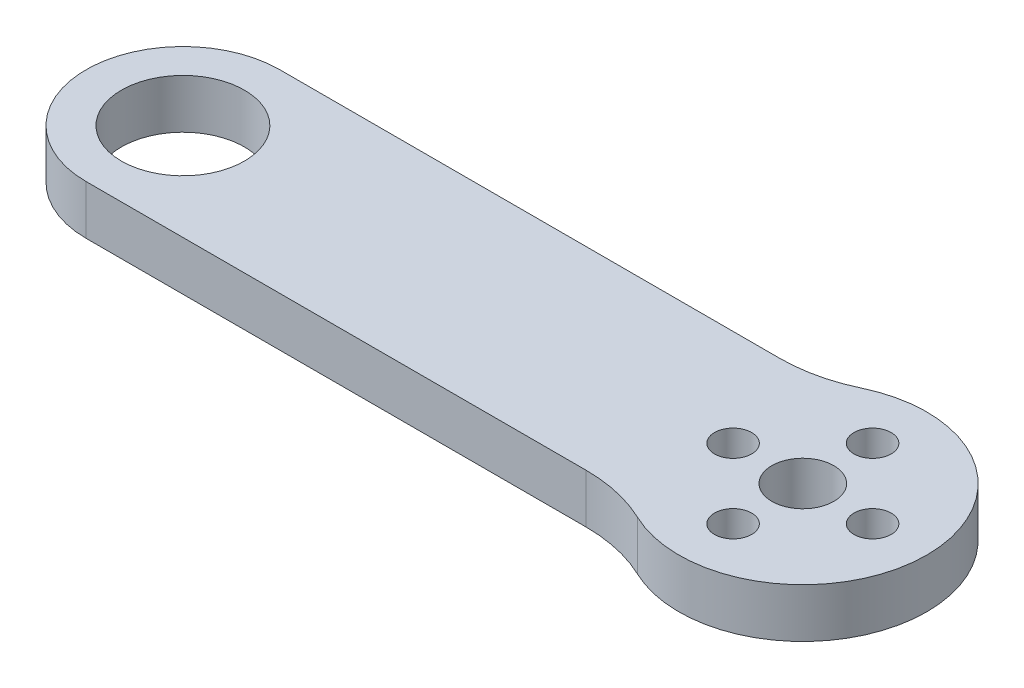
SolidWorks part; units mm, degrees
ref_plane "Front Plane" through (0, 0, 0) normal (0, 0, 1) x (1, 0, 0)
ref_plane "Top Plane" through (0, 0, 0) normal (0, 1, 0) x (1, 0, 0)
ref_plane "Right Plane" through (0, 0, 0) normal (1, 0, 0) x (0, 0, -1)
sketch "Sketch1" plane through (0, 0, 0) normal (0, 1, 0) x (1, 0, 0)
  line L0 (-7.7419, 6.25) -> (-40, 6.25)
  line L1 (0, 0) -> (-40, 0) construction
  line L2 (-40, -6.25) -> (-40, 6.25) construction
  line L3 (-40, -6.25) -> (-7.7419, -6.25)
  arc A0 (-3.4409, -7.2222) -> (-3.4409, 7.2222) centre (0, 0) ccw
  arc A1 (-40, -6.25) -> (-40, 6.25) centre (-40, 0) cw
  arc A2 (-7.7419, -6.25) -> (-3.4409, -7.2222) centre (-7.7419, -16.25) cw
  arc A3 (-7.7419, 6.25) -> (-3.4409, 7.2222) centre (-7.7419, 16.25) ccw
  circle A4 centre (-40, 0) radius 3.9687
  circle A5 centre (0, 0) radius 2
  point P9 (-40, 0)
  dimension "D1" = 16
  dimension "D2" = 10
  dimension "D5" = 7.9375
  dimension "D6" = 4
  dimension "D3" = 12.5
  dimension "D4" = 40
extrude "Boss-Extrude1" add sketch "Sketch1" along normal blind 3.175
hole_wizard "M2 Clearance Hole1" positions "Sketch2" profile "Sketch3" hole size "M2" standard "ANSI Metric" end condition through all
sketch "Sketch2" plane through (0, 3.175, 0) normal (0, 1, 0) x (1, 0, 0)
  circle A0 centre (0, 0) radius 4.5
  point P5 (0, 4.5)
  point P7 (4.5, 0)
  point P9 (0, -4.5)
  point P11 (-4.5, 0)
  dimension "D1" = 9
sketch "Sketch3" plane through (-4.5, 3.175, 0) normal (1, 0, 0) x (0, 0, 1)
  line L0 (0, 0) -> (0, 3.175)
  line L1 (0, 3.175) -> (1.2, 3.175)
  line L2 (1.2, 3.175) -> (1.2, 0)
  line L5 (1.2, 0) -> (0, 0)
  line L11 (0, -6.35) -> (0, 107.95) construction
  dimension "Thru Hole Dia." = 2.4
  dimension "Thru Hole Depth" = 3.175
